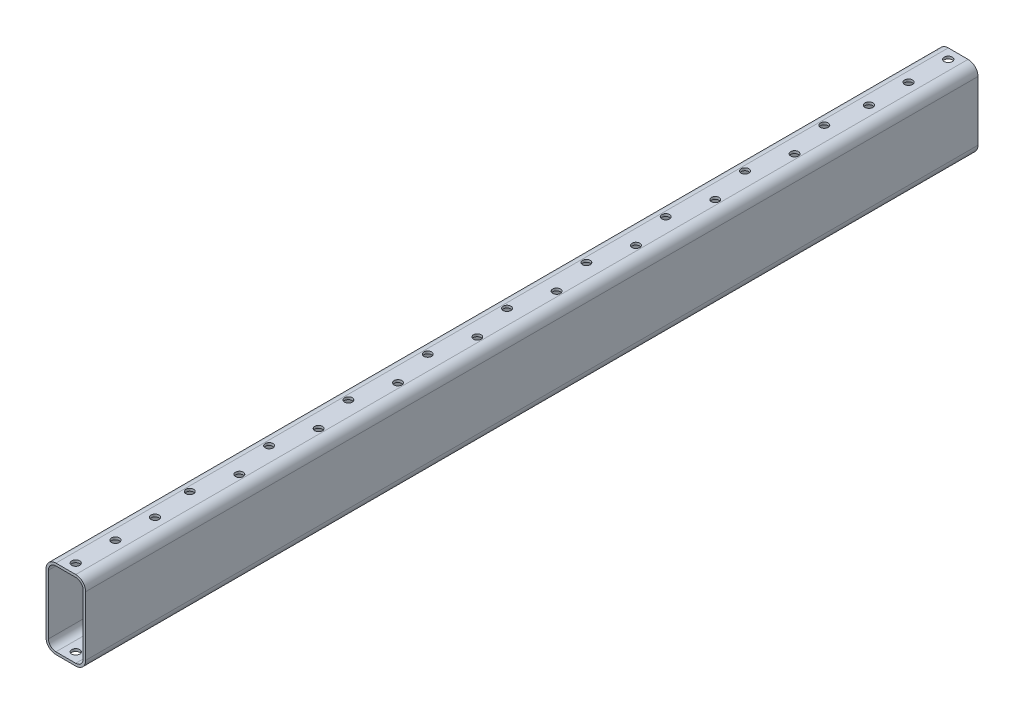
SolidWorks part; units mm, degrees
material "6061-T6 (SS)"
ref_plane "Front Plane" through (0, 0, 0) normal (0, 0, 1) x (1, 0, 0)
ref_plane "Top Plane" through (0, 0, 0) normal (0, 1, 0) x (1, 0, 0)
ref_plane "Right Plane" through (0, 0, 0) normal (1, 0, 0) x (0, 0, -1)
sketch "Sketch1" plane through (0, 0, 0) normal (0, 0, 1) x (1, 0, 0)
  line L1 (-6.35, -25.4) -> (6.35, -25.4)
  line L2 (-12.7, -19.05) -> (-12.7, 19.05)
  line L3 (-6.35, 25.4) -> (6.35, 25.4)
  line L4 (12.7, -19.05) -> (12.7, 19.05)
  line L5 (-12.7, -25.4) -> (12.7, 25.4) construction
  line L6 (-12.7, 25.4) -> (12.7, -25.4) construction
  arc A0 (-12.7, -19.05) -> (-6.35, -25.4) centre (-6.35, -19.05) ccw
  arc A1 (6.35, -25.4) -> (12.7, -19.05) centre (6.35, -19.05) ccw
  arc A2 (6.35, 25.4) -> (12.7, 19.05) centre (6.35, 19.05) cw
  arc A3 (-12.7, 19.05) -> (-6.35, 25.4) centre (-6.35, 19.05) cw
  point P0 (0, 0)
  dimension "D3" = 6.35
  dimension "D1" = 50.8
  dimension "D2" = 25.4
extrude "Extrude-Thin1" add sketch "Sketch1" along normal blind 571.5 thin thin type one direction reverse wall 1.5875
hole_wizard "#10 Clearance Hole1" positions "3DSketch1" profile "Sketch3" hole size "#10" standard "ANSI Inch" end condition through all
sketch3d "3DSketch1"
  line L1 (6.35, 25.4, 0) -> (-6.35, 25.4, 0) construction
  line L6 (0, 25.4, 571.5) -> (0, 25.4, 0) construction
  line L7 (6.35, 25.4, 571.5) -> (-6.35, 25.4, 571.5) construction
  point P57 (0, 25.4, 6.35)
  point P59 (0, 25.4, 31.75)
  point P61 (0, 25.4, 57.15)
  point P63 (0, 25.4, 539.75)
  point P65 (0, 25.4, 514.35)
  point P67 (0, 25.4, 565.15)
  dimension "D1" = 25.4
  dimension "D2" = 25.4
  dimension "D3" = 6.35
  dimension "D4" = 25.4
  dimension "D5" = 25.4
  dimension "D6" = 6.35
sketch "Sketch3" plane through (0, 25.4, 565.15) normal (1, 0, 0) x (0, 0, 1)
  line L0 (0, 0) -> (0, 50.8)
  line L1 (0, 50.8) -> (2.5527, 50.8)
  line L2 (2.5527, 50.8) -> (2.5527, 0)
  line L5 (2.5527, 0) -> (0, 0)
  line L11 (0, -6.35) -> (0, 107.95) construction
  dimension "Thru Hole Dia." = 5.1054
  dimension "Thru Hole Depth" = 50.8
hole_wizard "3/16 (0.195) Diameter Hole1" positions "Sketch4" profile "Sketch5" hole size "3/16" standard "ANSI Inch" end condition up to next
sketch "Sketch4" plane through (0, 25.4, 0) normal (0, 1, 0) x (1, 0, 0)
  point P145 (-3.175, -82.55)
  point P148 (3.175, -107.95)
  point P151 (-3.175, -133.35)
  point P154 (3.175, -158.75)
  point P157 (-3.175, -184.15)
  point P160 (3.175, -209.55)
  point P163 (-3.175, -234.95)
  point P166 (3.175, -260.35)
  point P169 (-3.175, -285.75)
  point P172 (3.175, -311.15)
  point P175 (-3.175, -336.55)
  point P178 (3.175, -361.95)
  point P181 (-3.175, -387.35)
  point P184 (3.175, -412.75)
  point P187 (-3.175, -438.15)
  point P190 (3.175, -463.55)
  point P193 (-3.175, -488.95)
sketch "Sketch5" plane through (-3.175, 25.4, 82.55) normal (1, 0, 0) x (0, 0, 1)
  line L0 (0, 0) -> (0, 1.5875)
  line L1 (0, 1.5875) -> (2.4765, 1.5875)
  line L2 (2.4765, 1.5875) -> (2.4765, 0)
  line L5 (2.4765, 0) -> (0, 0)
  line L11 (0, -6.35) -> (0, 107.95) construction
  dimension "Thru Hole Dia." = 4.953
  dimension "Thru Hole Depth" = 1.5875
